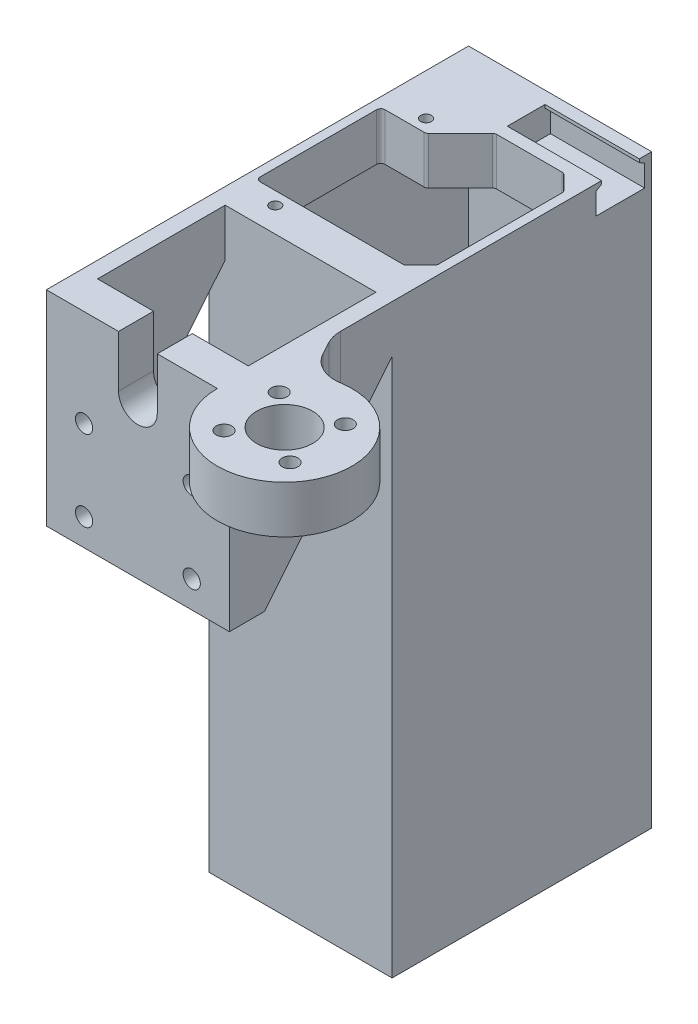
SolidWorks part; units mm, degrees
ref_plane "Front Plane" through (0, 0, 0) normal (0, 0, 1) x (1, 0, 0)
ref_plane "Top Plane" through (0, 0, 0) normal (0, 1, 0) x (1, 0, 0)
ref_plane "Right Plane" through (0, 0, 0) normal (1, 0, 0) x (0, 0, -1)
sketch "Sketch1" plane through (0, 0, 0) normal (0, 1, 0) x (1, 0, 0)
  line L0 (0, 0) -> (0, 59.6401) construction
  line L1 (-20, -19.2885) -> (-21.7, -19.2885)
  line L2 (20, 17.7115) -> (21.7, 17.7115)
  line L3 (20, 17.7115) -> (20, 69.9115)
  line L4 (20, 69.9115) -> (21.7, 69.9115)
  line L5 (21.7, 17.7115) -> (21.7, 69.9115)
  line L6 (20, 17.7115) -> (21.7, 17.7115)
  line L7 (20, 17.7115) -> (20, -19.2885)
  line L8 (20, -19.2885) -> (21.7, -19.2885)
  line L9 (21.7, 17.7115) -> (21.7, -19.2885)
  line L10 (-21.7, 17.7115) -> (-21.7, -19.2885)
  line L11 (-20, 17.7115) -> (-21.7, 17.7115)
  line L12 (-20, 17.7115) -> (-20, -19.2885)
  line L13 (-20, 69.9115) -> (-21.7, 69.9115)
  line L14 (-21.7, 17.7115) -> (-21.7, 69.9115)
  line L15 (-20, 17.7115) -> (-21.7, 17.7115)
  line L16 (-20, 17.7115) -> (-20, 69.9115)
  dimension "18" = 20
  dimension "D2" = 1.7
  dimension "D3" = 37
  dimension "D4" = 52.2
extrude "Boss-Extrude1" add sketch "Sketch1" against normal blind 8.8 from offset 1 contours L12 L11 L10 L1 | L11 L16 L13 L14 | L3 L2 L5 L4 offset against normal yes
sketch "Sketch4" plane through (0, -9.8, 0) normal (0, -1, 0) x (1, 0, 0)
  line L0 (-21.7, -69.9115) -> (-21.7, 19.2885) construction
  line L1 (12, -69.9115) -> (-21.7, -69.9115)
  line L2 (12, -69.9115) -> (12, -58.3115)
  line L3 (12, -58.3115) -> (-21.7, -58.3115)
  line L4 (-21.7, -69.9115) -> (-21.7, -58.3115)
  line L10 (-20, -69.9115) -> (-20, 19.2885) construction
  line L13 (-20, -69.9115) -> (-21.7, -69.9115) construction
  dimension "D1" = 11.6
  dimension "D2" = 32
extrude "Boss-Extrude3" add sketch "Sketch4" against normal up to surface (8.8 mm away)
sketch "Sketch3" plane through (0, -9.8, 0) normal (0, -1, 0) x (1, 0, 0)
  line L0 (-21.7, -69.9115) -> (-21.7, 19.2885) construction
  line L1 (-21.7, -58.9115) -> (-7.7, -58.9115)
  line L2 (-21.7, -58.9115) -> (-21.7, -51.9115)
  line L3 (-21.7, -51.9115) -> (-7.7, -51.9115)
  line L4 (-7.7, -58.9115) -> (-7.7, -51.9115)
  line L6 (0, 0) -> (0, -31.4212) construction
  line L13 (12, -69.9115) -> (-21.7, -69.9115) construction
  line L14 (-21.7, -40.3115) -> (-3.8096, -40.3115) construction
  line L15 (-21.7, -28.7115) -> (-7.7, -28.7115)
  line L16 (-7.7, -21.7115) -> (-7.7, -28.7115)
  line L17 (-21.7, -21.7115) -> (-7.7, -21.7115)
  line L18 (-21.7, -21.7115) -> (-21.7, -28.7115)
  line L19 (-20, -58.3115) -> (-20, 19.2885) construction
  circle A0 centre (-14, -54.3115) radius 1
  circle A2 centre (-14, -26.3115) radius 1
  dimension "D4" = 2.4
  dimension "D5" = 2
  dimension "D1" = 14
  dimension "D2" = 15.6
  dimension "D3" = 7
  dimension "D6" = 6
  dimension "D7" = 14
extrude "Servo Holder" add sketch "Sketch3" along normal blind 1 and the other way offset from surface (8.8 mm away) 1 other way up to plane "Top Plane"
sketch "Sketch37" plane through (0, -1, 0) normal (0, 1, 0) x (1, 0, 0)
  line L0 (-7.7, 21.7115) -> (-20, 21.7115) construction
  line L1 (12.3, 21.7115) -> (-7.7, 21.7115)
  line L2 (12.3, 21.7115) -> (12.3, 28.7115)
  line L3 (12.3, 28.7115) -> (-7.7, 28.7115)
  line L4 (-7.7, 21.7115) -> (-7.7, 28.7115)
  line L5 (-21.7, 69.9115) -> (-21.7, -19.2885) construction
  dimension "D1" = 34
extrude "Boss-Extrude19" add sketch "Sketch37" against normal up to surface (9.8 mm away) up to face at (-14.7, -10.8, -25.2115)
sketch "Sketch29" plane through (0, 0, -69.9115) normal (0, 0, -1) x (-1, 0, 0)
  line L1 (21.7, -9.8) -> (-12.7099, -9.8)
  line L2 (21.7, -9.8) -> (21.7, -16.1774)
  line L3 (21.7, -16.1774) -> (-12.7099, -16.1774)
  line L4 (-12.7099, -9.8) -> (-12.7099, -16.1774)
extrude "Cut-Extrude10" cut sketch "Sketch29" against normal through all both and the other way through all
sketch "Sketch30" plane through (0, 0, 0) normal (0, 0, 1) x (1, 0, 0)
  line L0 (-4.7, -1) -> (-4.7, -39) construction
  line L1 (12.3, -1) -> (-21.7, -1)
  line L2 (12.3, -1) -> (12.3, -39)
  line L3 (12.3, -39) -> (-21.7, -39)
  line L4 (-21.7, -1) -> (-21.7, -39)
  line L7 (-21.7, -1) -> (12.3, -1) construction
  line L9 (12.3, -1) -> (-20, -1) construction
  line L11 (-21.7, -9.8) -> (-21.7, -1) construction
  circle A0 centre (5.3, -34) radius 1.6
  circle A1 centre (5.3, -19) radius 1.6
  circle A2 centre (-14.7, -34) radius 1.6
  circle A3 centre (-14.7, -19) radius 1.6
  dimension "D2" = 10
  dimension "D4" = 15
  dimension "D1" = 17
  dimension "D3" = 38
  dimension "D5" = 18
  dimension "D6" = 10
extrude "Boss-Extrude13" add sketch "Sketch30" along normal blind 6.5 from offset 2 separate body
sketch "Sketch41" plane through (-20, 0, 0) normal (1, 0, 0) x (0, 0, -1)
  line L0 (21.7115, -1) -> (-19.2885, -1) construction
  line L1 (-2, -1) -> (-19.2885, -1)
  line L2 (-2, -1) -> (-2, -9.8)
  line L3 (-2, -9.8) -> (-19.2885, -9.8)
  line L4 (-19.2885, -1) -> (-19.2885, -9.8)
  line L5 (-2, -1) -> (-2, -39) construction
extrude "Cut-Extrude14" cut sketch "Sketch41" against normal blind 15
sketch "Sketch32" plane through (0, -39, 0) normal (0, -1, 0) x (1, 0, 0)
  line L1 (22.55, 8.5) -> (12.9564, 0.4867) construction
  line L2 (22.55, 8.5) -> (12.3, 8.5) construction
  line L4 (-21.7, 8.5) -> (12.3, 8.5) construction
  circle A0 centre (22.55, 8.5) radius 5.2
  circle A1 centre (22.55, 8.5) radius 12.5
  circle A2 centre (16.4101, 3.3715) radius 1.45
  circle A3 centre (17.4215, 14.6399) radius 1.45
  circle A4 centre (28.6899, 13.6285) radius 1.45
  circle A5 centre (27.6785, 2.3601) radius 1.45
  point P18 (22.55, 8.5)
  line M1 (-21.7, 2) -> (12.3, 2)
  line M2 (12.3, 2) -> (12.3, 8.5)
  line M3 (12.3, 8.5) -> (-21.7, 8.5)
  dimension "D1" = 8
  dimension "D2" = 25
  dimension "D4" = 10.4
  dimension "D5" = 10.25
  dimension "D3" = 4
extrude "Boss-Extrude14" add sketch "Sketch32" along normal blind 8.8 from surface at -38 contours A1 A5 A4 A3 A2 A0 M1 M3 M2 starting at face at (-3.85, -1, 5.25)
sketch "Sketch34" plane through (-21.7, 0, 0) normal (-1, 0, 0) x (0, 0, 1)
  line L1 (-21.7115, -1) -> (-21.7115, -9.8)
  line L5 (-69.9115, -1) -> (2, -1) construction
  line L7 (-21.7115, -9.8) -> (2, -39)
  line L8 (-21.7115, -9.8) -> (-21.7115, -1) construction
  line L9 (2, -39) -> (8.5, -39)
  line L10 (8.5, -39) -> (8.5, -1)
  line L11 (8.5, -1) -> (-21.7115, -1)
extrude "Boss-Extrude16" add sketch "Sketch34" against normal blind 3
sketch "Sketch35" plane through (12.3, 0, 0) normal (1, 0, 0) x (0, 0, -1)
  line L0 (-2, -1) -> (21.7115, -1)
  line L1 (21.7115, -1) -> (21.7115, -9.8)
  line L3 (-8.5, -9.8) -> (-8.5, -1)
  line L4 (-8.5, -1) -> (-2, -1)
  line L5 (21.7115, -9.8) -> (21.7115, -1) construction
  line L8 (-8.5, -39) -> (-8.5, -9.8) construction
  line L9 (21.7115, -1) -> (28.7115, -1) construction
  line L10 (21.7115, -9.8) -> (-2, -39)
  line L11 (-2, -39) -> (-8.5, -39)
  line L12 (-8.5, -39) -> (-8.5, -9.8)
extrude "Boss-Extrude17" add sketch "Sketch35" against normal blind 3
sketch "Sketch36" plane through (0, -9.8, 0) normal (0, -1, 0) x (1, 0, 0)
  line L0 (12.3, -10.5792) -> (16.6342, -2.5115)
  line L2 (16.6342, -2.5115) -> (12.3, 1.3455)
  line L3 (12.3, 1.3455) -> (12.3, -10.5792)
  line L4 (22.55, 8.5) -> (12.3, -10.5792) construction
  line L5 (12.3, 8.5) -> (12.3, 2) construction
  arc A1 (12.3, 1.3455) -> (10.05, 8.5) centre (22.55, 8.5) ccw construction
extrude "Boss-Extrude18" add sketch "Sketch36" against normal up to surface (8.8 mm away) up to face at (-4.7, -1, -9.8558)
fillet "Fillet9" [suppressed] radius 1
sketch "Sketch39" plane through (0, -1, 0) normal (0, 1, 0) x (1, 0, 0)
  line L0 (-21.7, 69.9115) -> (12, 69.9115) construction
  line L1 (12.3, 28.7115) -> (10.6, 28.7115)
  line L2 (12.3, 28.7115) -> (12.3, 69.9115)
  line L3 (12.3, 69.9115) -> (10.6, 69.9115)
  line L4 (10.6, 28.7115) -> (10.6, 69.9115)
  line L5 (-20, 28.7115) -> (12.3, 28.7115) construction
  line L6 (12.3, 10.5792) -> (12.3, 28.7115) construction
  point P7 (12.3, 49.3115)
  dimension "D1" = 1.7
extrude "Boss-Extrude20" add sketch "Sketch39" against normal up to surface (8.8 mm away)
sketch "Sketch40" plane through (12.3, 0, 0) normal (1, 0, 0) x (0, 0, -1)
  line L1 (60.6115, -1) -> (67.6115, -1)
  line L6 (60.6115, -2.2) -> (59.6115, -2.2)
  line L7 (59.6115, -2.2) -> (59.6115, -6.2)
  line L8 (59.6115, -6.2) -> (68.6115, -6.2)
  line L9 (64.1115, -6.2) -> (64.1115, -1)
  line L11 (68.6115, -2.2) -> (68.6115, -6.2)
  line L12 (67.6115, -2.2) -> (68.6115, -2.2)
  line L13 (67.6115, -1) -> (67.6115, -2.2)
  line L14 (69.9115, -9.8) -> (69.9115, -1) construction
  line L15 (60.6115, -2.2) -> (60.6115, -1)
  line L16 (10.5792, -1) -> (69.9115, -1) construction
  point P9 (59.6115, -4.2)
  dimension "D1" = 5.8
  dimension "D2" = 3.5
  dimension "D3" = 4.5
  dimension "D4" = 4
  dimension "D5" = 1.2
  dimension "D6" = 3.5
  dimension "D7" = 1
extrude "Cut-Extrude13" cut sketch "Sketch40" against normal blind 17.5
chamfer "Chamfer2" distance 0.6 angle 60 2 edges at (3.55, -2.2, -67.6115) (3.55, -2.2, -60.6115)
chamfer "Chamfer3" distance 3 angle 45 2 edges at (10.6, -5.4, -28.7115) (10.6, -5.4, -58.3115)
fillet "Fillet10" radius 6 2 edges at (16.6342, -5.4, -2.5115) (12.3, -5.4, -10.5792)
sketch "Sketch42" plane through (0, 0, 8.5) normal (0, 0, 1) x (1, 0, 0)
  line L0 (-4.7, -39) -> (-4.7, -1) construction
  line L3 (-21.7, -39) -> (12.3, -39) construction
  line L4 (10.05, -1) -> (-21.7, -1) construction
  line L5 (-1.1, -1) -> (-1.1, -10.6)
  line L6 (-8.3, -1) -> (-8.3, -10.6)
  line L7 (-1.1, -1) -> (-8.3, -1)
  arc A0 (-1.1, -10.6) -> (-8.3, -10.6) centre (-4.7, -10.6) cw
  point P11 (-4.7, -14.2)
  dimension "D1" = 3.6
  dimension "D2" = 13.2
extrude "Cut-Extrude15" cut sketch "Sketch42" against normal blind 10
chamfer "Chamfer4" distance 2.5 angle 45 1 edges at (-7.7, -5.4, -58.3115)
sketch "Sketch43" plane through (0, -1, 0) normal (0, 1, 0) x (1, 0, 0)
  line L0 (-5.2, 58.3115) -> (-11.6, 51.9115)
  line L1 (-7.7, 51.9115) -> (-20, 51.9115) construction
  line L2 (-11.6, 51.9115) -> (-5.2, 51.9115)
  line L3 (-5.2, 51.9115) -> (-5.2, 58.3115)
extrude "Cut-Extrude16" cut sketch "Sketch43" against normal blind 10
fillet "Fillet11" radius 0.8 8 edges at (-20, -5.4, -51.9115) (-20, -5.4, -28.7115) (7.6, -5.4, -28.7115) (10.6, -5.4, -31.7115) (10.6, -5.4, -55.3115) (7.6, -5.4, -58.3115) (-11.6, -5.4, -51.9115) (-5.2, -5.4, -58.3115)
sketch "Sketch44" plane through (0, -9.8, 0) normal (0, -1, 0) x (-1, 0, 0)
  line L0 (-12.3, 69.9115) -> (-12.3, 21.7115)
  line L1 (-12.3, 21.7115) -> (21.7, 21.7115)
  line L2 (21.7, 21.7115) -> (21.7, 69.9115)
  line L3 (21.7, 69.9115) -> (-12.3, 69.9115)
  line L4 (-10.9, 68.5115) -> (-10.9, 23.1115)
  line L5 (-10.9, 23.1115) -> (20.3, 23.1115)
  line L6 (20.3, 23.1115) -> (20.3, 68.5115)
  line L7 (20.3, 68.5115) -> (-10.9, 68.5115)
  line L8 (-12.3, 12.0888) -> (-12.3, 60.6115) construction
  dimension "D1" = 1.4
  dimension "D2" = 1.4
  dimension "D3" = 1.4
  dimension "D4" = 1.4
extrude "Boss-Extrude21" add sketch "Sketch44" along normal blind 100
